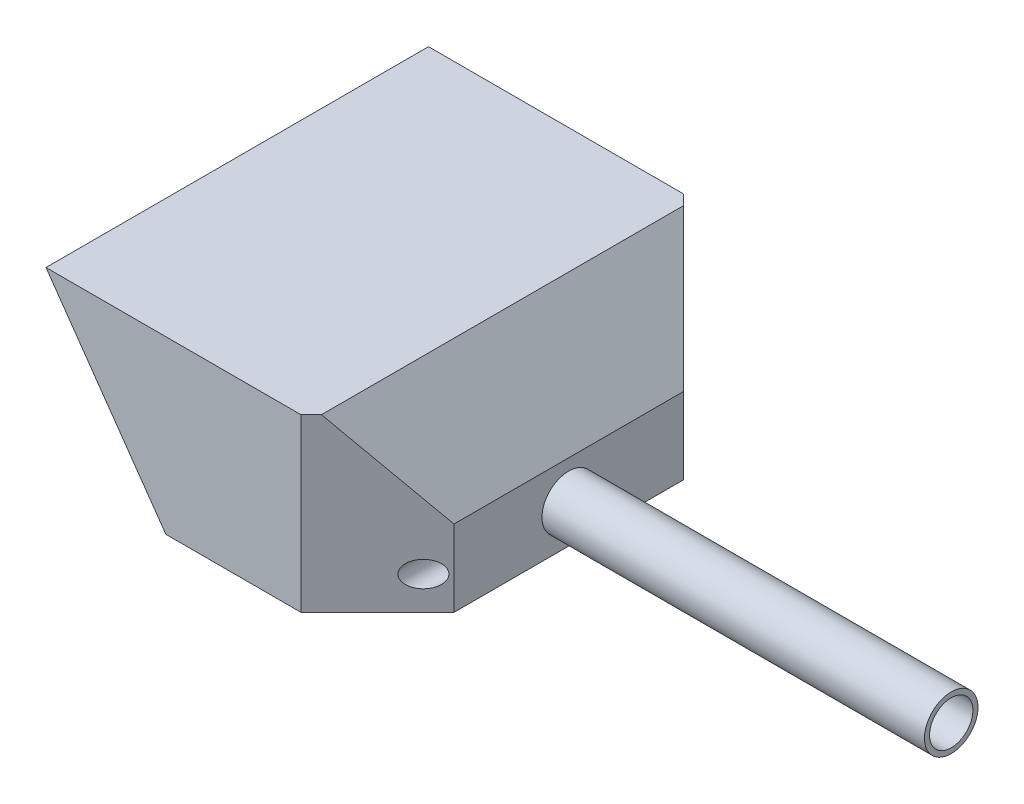
SolidWorks part; units mm, degrees
ref_plane "前视基准面" through (0, 0, 0) normal (0, 0, 1) x (1, 0, 0)
ref_plane "上视基准面" through (0, 0, 0) normal (0, 1, 0) x (1, 0, 0)
ref_plane "右视基准面" through (0, 0, 0) normal (1, 0, 0) x (0, 0, -1)
sketch "草图1" plane through (0, 0, 0) normal (0, 0, 1) x (1, 0, 0)
  line L0 (0, 0) -> (-59, 0)
  line L1 (-59, 0) -> (-106, 67.123)
  line L2 (-106, 67.123) -> (-1.9938, 67.123)
  line L3 (-1.9938, 67.123) -> (24, 30)
  line L4 (24, 30) -> (24, 0)
  line L5 (24, 0) -> (0, 0)
  dimension "D1" = 130
  dimension "D2" = 83
  dimension "D3" = 55
  dimension "D4" = 30
  dimension "D5" = 24
extrude "凸台-拉伸1" add sketch "草图1" along normal mid plane 150
sketch "草图2" plane through (24, 0, 0) normal (1, 0, 0) x (0, 0, -1)
  line L0 (-75, 0) -> (75, 0) construction
  circle A0 centre (0, 15) radius 10.5
  circle A1 centre (0, 15) radius 8.5
  dimension "D1" = 21
  dimension "D2" = 17
  dimension "D3" = 15
extrude "凸台-拉伸2" add sketch "草图2" along normal blind 150
chamfer "倒角1" distance 30 angle 45 2 edges at (24, 15, 75) (24, 15, -75)
sketch "草图3" plane through (0, 0, 0) normal (0, 0, 1) x (1, 0, 0)
  line L0 (24, 0) -> (-6, 0) construction
  line L1 (24, 4.5) -> (24, 25.5) construction
  circle A0 centre (18, 13) radius 5
  dimension "D1" = 10
  dimension "D3" = 6
  dimension "D2" = 13
extrude "切除-拉伸1" cut sketch "草图3" against normal through all and the other way through all
